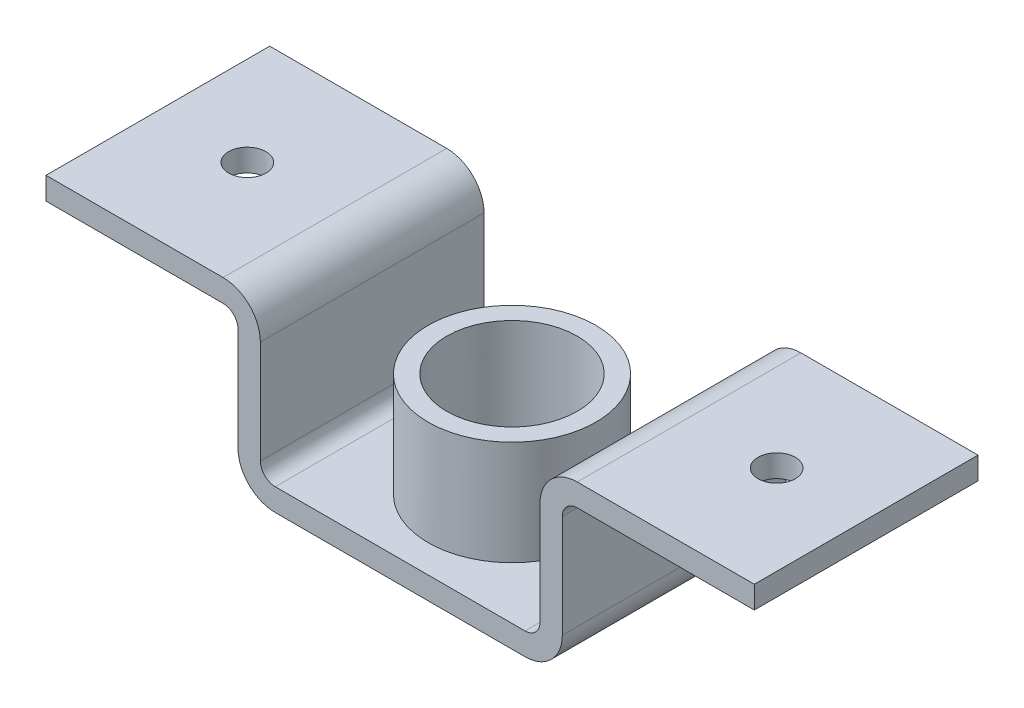
SolidWorks part; units mm, degrees
ref_plane "Front Plane" through (0, 0, 0) normal (0, 0, 1) x (1, 0, 0)
ref_plane "Top Plane" through (0, 0, 0) normal (0, 1, 0) x (1, 0, 0)
ref_plane "Right Plane" through (0, 0, 0) normal (1, 0, 0) x (0, 0, -1)
sketch "Sketch1" plane through (0, 0, 0) normal (0, 0, 1) x (1, 0, 0)
  line L0 (167.5, 0) -> (-167.5, 0)
  line L1 (-217.5, 50) -> (-217.5, 188)
  line L2 (-237.5, 208) -> (-475, 208)
  line L3 (-475, 208) -> (-475, 238)
  line L4 (-475, 238) -> (-237.5, 238)
  line L5 (-187.5, 188) -> (-187.5, 50)
  line L6 (-167.5, 30) -> (167.5, 30)
  line L8 (0, 317.5462) -> (0, -92.4324) construction
  line L9 (187.5, 188) -> (187.5, 50)
  line L10 (475, 238) -> (237.5, 238)
  line L11 (475, 208) -> (475, 238)
  line L12 (237.5, 208) -> (475, 208)
  line L13 (217.5, 50) -> (217.5, 188)
  arc A0 (-167.5, 0) -> (-217.5, 50) centre (-167.5, 50) cw
  arc A1 (-167.5, 30) -> (-187.5, 50) centre (-167.5, 50) cw
  arc A2 (-217.5, 188) -> (-237.5, 208) centre (-237.5, 188) ccw
  arc A3 (-187.5, 188) -> (-237.5, 238) centre (-237.5, 188) ccw
  arc A4 (187.5, 188) -> (237.5, 238) centre (237.5, 188) cw
  arc A5 (217.5, 188) -> (237.5, 208) centre (237.5, 188) cw
  arc A6 (167.5, 30) -> (187.5, 50) centre (167.5, 50) ccw
  arc A7 (167.5, 0) -> (217.5, 50) centre (167.5, 50) ccw
  point P11 (0, 317.5462)
  point P21 (0, 30)
  point P22 (0, 0)
  point P32 (-997.2674, 135.9993)
  dimension "D7" = 50
  dimension "D8" = 20
  dimension "D9" = 20
  dimension "D10" = 50
  dimension "D1" = 30
  dimension "D2" = 30
  dimension "D3" = 30
  dimension "D4" = 475
  dimension "D5" = 187.5
  dimension "D6" = 238
extrude "Boss-Extrude2" add sketch "Sketch1" along normal blind 300
sketch "Sketch3" plane through (0, 0, 0) normal (0, 1, 0) x (1, 0, 0)
  line L0 (475, -300) -> (237.5, -300) construction
  line L1 (475, -300) -> (475, 0) construction
  line L2 (-475, -300) -> (-475, 0) construction
  line L3 (167.5, -300) -> (-167.5, -300) construction
  circle A0 centre (0, -150) radius 37.5
  circle A1 centre (0, -150) radius 87.5
  circle A2 centre (0, -150) radius 112.5
  circle A3 centre (355, -150) radius 25
  circle A4 centre (-355, -150) radius 25
  point P8 (0, 0)
  dimension "D1" = 50
  dimension "D2" = 50
  dimension "D3" = 75
  dimension "D4" = 175
  dimension "D5" = 225
  dimension "D6" = 150
  dimension "D7" = 120
  dimension "D8" = 120
  dimension "D9" = 150
  dimension "D10" = 475
extrude "Boss-Extrude3" add sketch "Sketch3" along normal blind 170 contours A2 A1 region at (-109.318, 0, 150)
extrude "Cut-Extrude1" cut sketch "Sketch3<3>" along normal up to surface (238 mm away) contours A4 up to face at (-356.25, 238, 150)
sketch "Sketch3<3>" plane through (0, 0, 0) normal (0, 1, 0) x (1, 0, 0) same geometry as "Sketch3"
extrude "Cut-Extrude2" cut sketch "Sketch3<4>" along normal up to surface (238 mm away) contours A3 up to face at (356.25, 238, 150)
sketch "Sketch3<4>" plane through (0, 0, 0) normal (0, 1, 0) x (1, 0, 0) same geometry as "Sketch3"
extrude "Cut-Extrude4" cut sketch "Sketch3<6>" along normal up to surface (30 mm away) contours A0 up to face at (0, 30, 37.5)
sketch "Sketch3<6>" plane through (0, 0, 0) normal (0, 1, 0) x (1, 0, 0) same geometry as "Sketch3"
